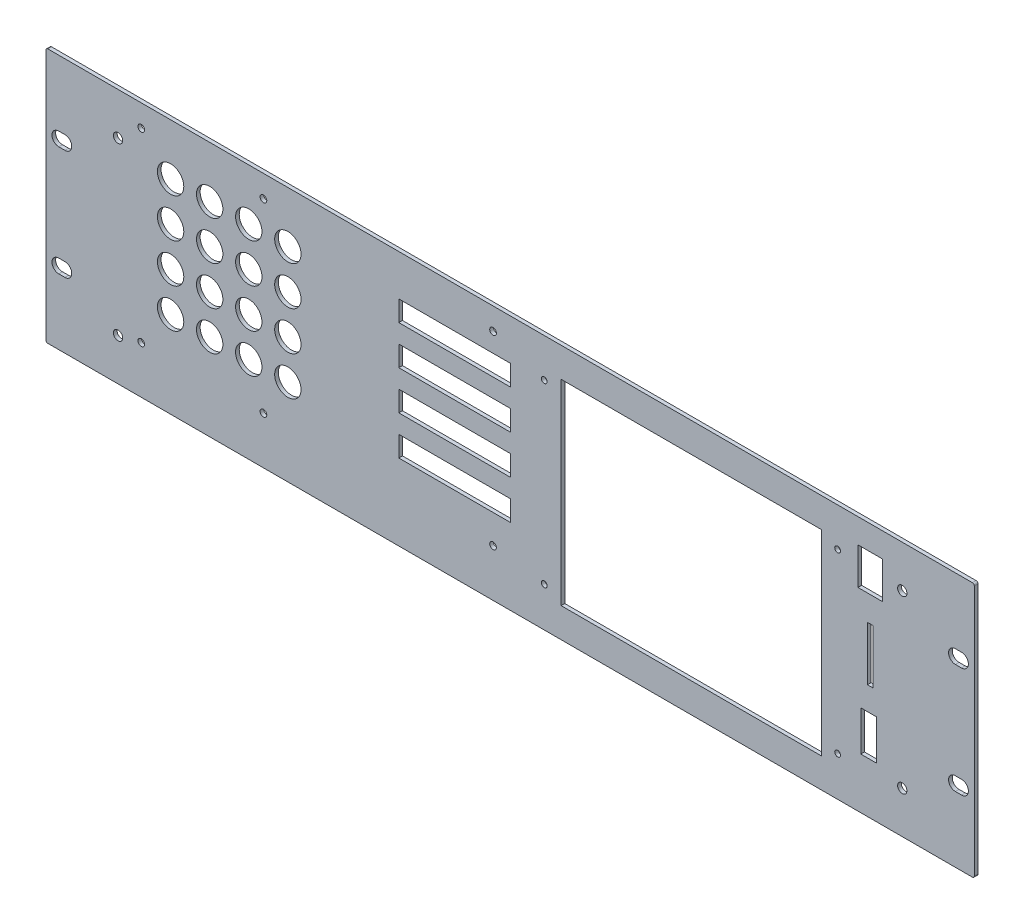
SolidWorks part; units mm, degrees
note: The reader was unsure of these and kept them because the rebuilt part matched: thickness of "Front Panel".
ref_plane "Front" through (0, 0, 0) normal (0, 0, 1) x (1, 0, 0)
ref_plane "Top" through (0, 0, 0) normal (0, 1, 0) x (1, 0, 0)
ref_plane "Right" through (0, 0, 0) normal (1, 0, 0) x (0, 0, -1)
sketch "Sketch1" plane through (0, 0, 0) normal (0, 0, 1) x (1, 0, 0)
  line L1 (1.016, 0) -> (481.584, 0)
  line L2 (0, 1.016) -> (0, 131.572)
  line L3 (1.016, 132.588) -> (481.584, 132.588)
  line L4 (482.6, 1.016) -> (482.6, 131.572)
  arc A0 (0, 131.572) -> (1.016, 132.588) centre (1.016, 131.572) cw
  arc A1 (1.016, 0) -> (0, 1.016) centre (1.016, 1.016) cw
  arc A2 (481.584, 0) -> (482.6, 1.016) centre (481.584, 1.016) ccw
  arc A3 (481.584, 132.588) -> (482.6, 131.572) centre (481.584, 131.572) cw
  point P6 (0, 132.588)
  point P9 (0, 0)
  point P12 (482.6, 0)
  dimension "D3" = 1.016
  dimension "U Height" = 132.588
  dimension "Panel Std Width" = 482.6
sheet metal parameters "Sheet-Metal1" thickness 1.905 parameters "D1"=1.778
base flange "Front Panel" sketch "Sketch1" thickness 1.905 parameters "D1"=1.778
sketch "Sketch2" plane through (0, 0, 1.905) normal (0, 0, 1) x (1, 0, 0)
  line L0 (8.2423, 41.2369) -> (8.2423, 34.1503) construction
  line L1 (0, 131.572) -> (0, 1.016) construction
  line L2 (482.6, 66.294) -> (0, 66.294) construction
  line L3 (472.7575, 34.1503) -> (475.9579, 34.1503)
  line L4 (241.3, 132.588) -> (241.3, 0) construction
  line L5 (481.584, 132.588) -> (1.016, 132.588) construction
  line L6 (475.9579, 41.2369) -> (472.7575, 41.2369)
  line L7 (9.8425, 98.4377) -> (6.6421, 98.4377)
  line L8 (6.6421, 91.3511) -> (9.8425, 91.3511)
  line L9 (6.6421, 41.2369) -> (9.8425, 41.2369)
  line L10 (9.8425, 34.1503) -> (6.6421, 34.1503)
  line L11 (1.016, 0) -> (481.584, 0) construction
  line L12 (475.9579, 91.3511) -> (472.7575, 91.3511)
  line L13 (472.7575, 98.4377) -> (475.9579, 98.4377)
  line L22 (482.6, 1.016) -> (482.6, 131.572) construction
  arc A0 (472.7575, 34.1503) -> (472.7575, 41.2369) centre (472.7575, 37.6936) cw
  arc A1 (475.9579, 41.2369) -> (475.9579, 34.1503) centre (475.9579, 37.6936) cw
  arc A2 (9.8425, 98.4377) -> (9.8425, 91.3511) centre (9.8425, 94.8944) cw
  arc A3 (6.6421, 91.3511) -> (6.6421, 98.4377) centre (6.6421, 94.8944) cw
  arc A4 (6.6421, 41.2369) -> (6.6421, 34.1503) centre (6.6421, 37.6936) ccw
  arc A5 (9.8425, 34.1503) -> (9.8425, 41.2369) centre (9.8425, 37.6936) ccw
  arc A6 (475.9579, 91.3511) -> (475.9579, 98.4377) centre (475.9579, 94.8944) ccw
  arc A7 (472.7575, 98.4377) -> (472.7575, 91.3511) centre (472.7575, 94.8944) ccw
  point P32 (13.3858, 37.6936)
  point P39 (3.0988, 37.6936)
  dimension "D1" = 28.6004
  dimension "D2" = 10.287
  dimension "D3" = 13.3858
  dimension "Slot Radius" = 3.5433
sketch "Sketch5" plane through (0, 0, 1.905) normal (0, 0, 1) x (1, 0, 0)
  line L2 (241.3, 132.588) -> (241.3, 0) construction
  line L3 (481.584, 132.588) -> (1.016, 132.588) construction
  line L4 (1.016, 0) -> (481.584, 0) construction
  line L5 (482.6, 66.294) -> (0, 66.294) construction
  line L6 (482.6, 1.016) -> (482.6, 131.572) construction
  line L7 (0, 131.572) -> (0, 1.016) construction
  circle A0 centre (445.135, 21.844) radius 2.4257
  circle A1 centre (37.465, 21.844) radius 2.4257
  circle A2 centre (37.465, 110.744) radius 2.4257
  circle A3 centre (445.135, 110.744) radius 2.4257
  circle A4 centre (241.3, -19.907) radius 2.0701
  dimension "D1" = 41.751
  dimension "8-32 Clear. Holes" = 4.8514
  dimension "D2" = 4.1402
  dimension "Panel Mounts Horizontal Location" = 203.835
  dimension "Panel Mounts Vertical Location" = 44.45
extrude "Front Panel Mounting Holes" cut sketch "Sketch5" against normal blind 1.905 normal cut yes
extrude "Rack Mounting Slot" cut sketch "Sketch2" against normal blind 1.905 normal cut yes
flat pattern "Flat-Pattern1"
sketch "Bend-Lines1" plane through (0, 0, 0) normal (0, 1, 0) x (-1, 0, 0)
sketch "ADio mounting holes" plane through (0, 0, 1.905) normal (0, 0, 1) x (1, 0, 0)
  circle A0 centre (49.53, 121.158) radius 1.7399
  circle A1 centre (113.03, 121.158) radius 1.7399
  circle A2 centre (232.41, 121.158) radius 1.7399
  circle A3 centre (49.53, 24.638) radius 1.7399
  circle A4 centre (113.03, 24.638) radius 1.7399
  circle A5 centre (232.41, 24.638) radius 1.7399
  circle A6 centre (49.53, 121.158) radius 1.778 construction
  circle A7 centre (113.03, 121.158) radius 1.778 construction
  circle A8 centre (232.41, 121.158) radius 1.778 construction
  circle A9 centre (49.53, 24.638) radius 1.778 construction
  dimension "D1" = 3.4798
  dimension "D2" = 3.4798
  dimension "D3" = 3.4798
  dimension "D4" = 3.4798
  dimension "D5" = 3.4798
  dimension "D6" = 3.4798
extrude "Cut-Extrude1" cut sketch "ADio mounting holes" against normal blind 2.54 normal cut yes
sketch "Sketch8" plane through (0, 0, 1.905) normal (0, 0, 1) x (1, 0, 0)
  circle A0 centre (64.77, 105.918) radius 6.858
  circle A2 centre (64.77, 105.918) radius 0.5 construction
  dimension "D1" = 13.716
extrude "BNC seed hole" cut sketch "Sketch8" against normal blind 2.54 normal cut yes
pattern_linear "BNC pattern" count 4 spacing 20.32 along (1, 0, 0) count 4 spacing 20.32 along (0, -1, 0) of "BNC seed hole"
sketch "Sketch9" plane through (0, 0, 1.905) normal (0, 0, 1) x (1, 0, 0)
  line L1 (183.388, 111.252) -> (241.427, 111.252)
  line L2 (183.388, 111.252) -> (183.388, 100.584)
  line L3 (183.388, 100.584) -> (241.427, 100.584)
  line L4 (241.427, 111.252) -> (241.427, 100.584)
  line L5 (184.15, 101.346) -> (212.09, 101.346) construction
  line L6 (240.665, 101.346) -> (240.665, 110.49) construction
  line L7 (184.15, 110.49) -> (184.15, 101.346) construction
  line L8 (240.665, 110.49) -> (212.725, 110.49) construction
  dimension "D4" = 0.762
  dimension "D1" = 0.762
  dimension "D2" = 0.762
  dimension "D3" = 0.762
extrude "DIO Seed Hole" cut sketch "Sketch9" against normal blind 2.54 normal cut yes
pattern_linear "DIO Pattern" count 4 spacing 20.32 along (0, -1, 0) of "DIO Seed Hole"
sketch "LCD view cutout" plane through (0, 0, 1.905) normal (0, 0, 1) x (1, 0, 0)
  line L1 (267.804, 117.244) -> (403.264, 117.244)
  line L2 (267.804, 117.244) -> (267.804, 15.344)
  line L3 (267.804, 15.344) -> (403.264, 15.344)
  line L4 (403.264, 117.244) -> (403.264, 15.344)
  line L6 (403.01, 117.498) -> (267.55, 117.498) construction
  line L7 (403.01, 15.598) -> (403.01, 117.498) construction
  line L8 (267.55, 15.598) -> (403.01, 15.598) construction
  line L9 (267.55, 117.498) -> (267.55, 15.598) construction
  dimension "D1" = 0.254
  dimension "D2" = 0.254
  dimension "D3" = 0.254
  dimension "D4" = 0.254
extrude "LCD Cutout" cut sketch "LCD view cutout" against normal blind 2.54 normal cut yes
sketch "LCD mount holes" plane through (0, 0, 1.905) normal (0, 0, 1) x (1, 0, 0)
  circle A0 centre (259.03, 20.598) radius 1.75 construction
  circle A1 centre (259.03, 112.498) radius 1.5
  circle A2 centre (411.53, 112.498) radius 1.5
  circle A3 centre (259.03, 20.598) radius 1.5
  circle A4 centre (411.53, 20.598) radius 1.5
  circle A5 centre (411.53, 20.598) radius 1.75 construction
  circle A6 centre (411.53, 112.498) radius 1.75 construction
  circle A7 centre (259.03, 112.498) radius 1.75 construction
  dimension "D1" = 3
  dimension "D2" = 3
  dimension "D3" = 3
  dimension "D4" = 3
extrude "LCD mount hole - cut" cut sketch "LCD mount holes" against normal blind 2.54 normal cut yes
sketch "Sketch10" plane through (0, 0, 1.905) normal (0, 0, 1) x (1, 0, 0)
  line L0 (481.584, 132.588) -> (1.016, 132.588) construction
  line L1 (422.075, 119.888) -> (434.975, 119.888)
  line L2 (422.075, 119.888) -> (422.075, 100.688)
  line L3 (422.075, 100.688) -> (434.975, 100.688)
  line L4 (434.975, 119.888) -> (434.975, 100.688)
  line L5 (482.6, 1.016) -> (482.6, 131.572) construction
  dimension "D1" = 12.9
  dimension "D2" = 19.2
  dimension "D3" = 12.7
  dimension "D4" = 47.625
extrude "power sw - cut" cut sketch "Sketch10" against normal blind 12.03 normal cut yes
sketch "Sketch11" plane through (0, 0, 1.905) normal (0, 0, 1) x (1, 0, 0)
  line L0 (427.0444, 59.3558) -> (431.4444, 59.3558) construction
  line L1 (427.0444, 87.4558) -> (429.9798, 87.4558)
  line L2 (427.0444, 87.4558) -> (427.0444, 59.3558)
  line L3 (427.0444, 59.3558) -> (429.9798, 59.3558)
  line L4 (429.9798, 87.4558) -> (429.9798, 59.3558)
  line L5 (423.8244, 46.9858) -> (431.4444, 46.9858) construction
  line L6 (423.5704, 47.2398) -> (431.6984, 47.2398)
  line L7 (423.5704, 47.2398) -> (423.5704, 26.4118)
  line L8 (423.5704, 26.4118) -> (431.6984, 26.4118)
  line L9 (431.6984, 47.2398) -> (431.6984, 26.4118)
  line L10 (423.8244, 26.6658) -> (431.4444, 26.6658) construction
  line L11 (431.4444, 26.6658) -> (431.4444, 36.8258) construction
  line L12 (423.8244, 26.6658) -> (423.8244, 36.8258) construction
  point P10 (427.6344, 46.9858)
  dimension "D1" = 0
  dimension "D2" = 0.254
  dimension "D3" = 0.254
  dimension "D4" = 0.254
  dimension "D5" = 0.254
extrude "Cut-Extrude8" cut sketch "Sketch11" against normal blind 2.54 normal cut yes
ref_plane "LCD Center Plane YZ" through (335.28, 0, 0) normal (1, 0, 0) x (0, 0, -1)
ref_plane "LCD center Plane YX" through (0, 66.548, 0) normal (0, 1, 0) x (-1, 0, 0)
ref_plane "ADIO left plane" through (43.18, 0, 0) normal (-1, 0, 0) x (0, 0, 1)
ref_plane "ADIO top plane" through (0, 127.508, 0) normal (0, 1, 0) x (-1, 0, 0)
